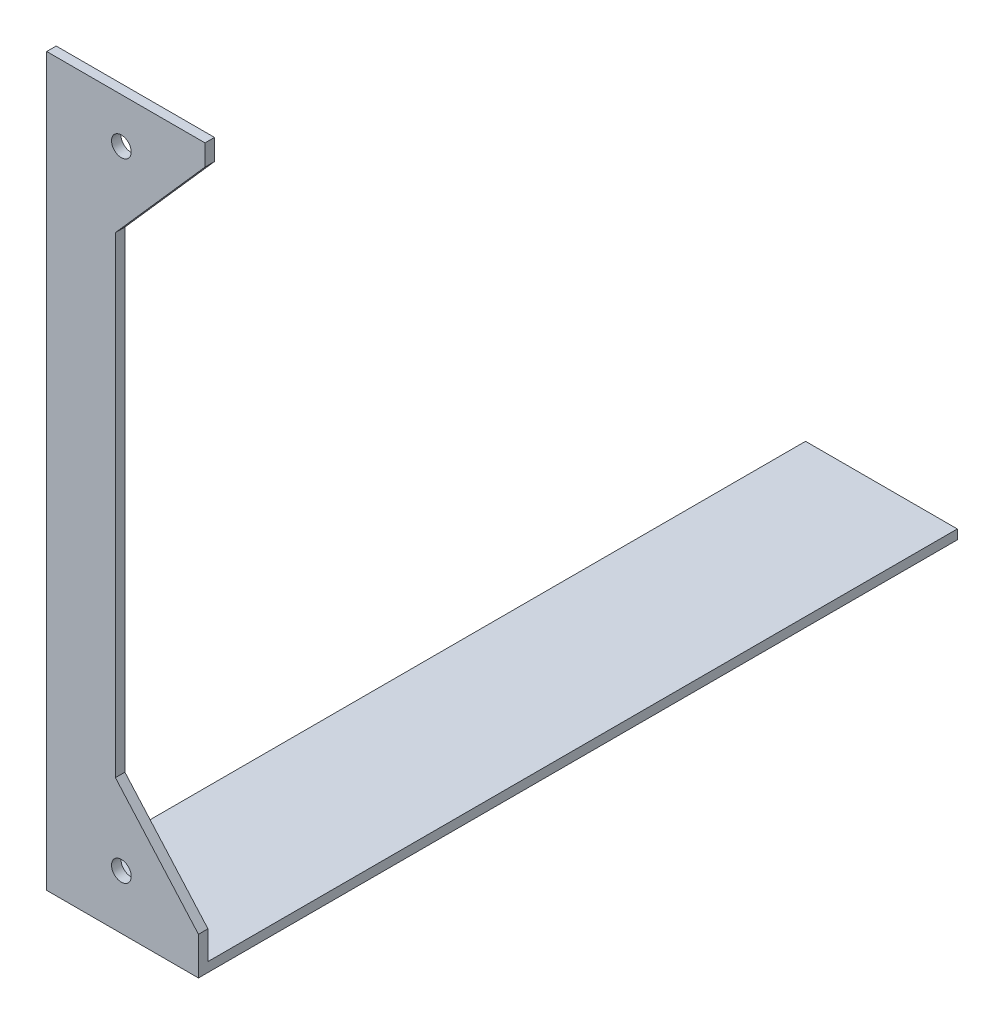
SolidWorks part; units mm, degrees
ref_plane "Front Plane" through (0, 0, 0) normal (0, 0, 1) x (1, 0, 0)
ref_plane "Top Plane" through (0, 0, 0) normal (0, 1, 0) x (1, 0, 0)
ref_plane "Right Plane" through (0, 0, 0) normal (1, 0, 0) x (0, 0, -1)
sketch "Sketch1" plane through (0, 0, 0) normal (0, 0, 1) x (1, 0, 0)
  line L0 (-250, 120) -> (0, 120) construction
  line L1 (-238.5, 99.5) -> (-223.5, 116.5) construction
  line L2 (-244.6, 99.5) -> (-238.5, 99.5) construction
  line L3 (-244.6, 20.5) -> (-244.6, 99.5) construction
  line L4 (-250, 2) -> (-250, 118) construction
  line L5 (0, 0) -> (-250, 0) construction
  line L6 (-238.5, 20.5) -> (-244.6, 20.5) construction
  line L7 (-223.5, 3.5) -> (-238.5, 20.5) construction
  line L8 (-250, 120) -> (-223.5, 120)
  line L9 (-238.5, 99.5) -> (-223.5, 116.5)
  line L10 (-244.6, 99.5) -> (-238.5, 99.5)
  line L11 (-244.6, 20.5) -> (-244.6, 99.5)
  line L12 (-250, 0) -> (-250, 120)
  line L13 (-223.5, 0) -> (-250, 0)
  line L14 (-238.5, 20.5) -> (-244.6, 20.5)
  line L15 (-223.5, 3.5) -> (-238.5, 20.5)
  line L16 (-223.5, 116.5) -> (-223.5, 120)
  line L17 (-223.5, 3.5) -> (-223.5, 0)
  line L18 (-238.5, 20.5) -> (-238.5, 99.5)
  line L19 (-224.6, 4.7467) -> (-224.6, 0)
  arc A0 (-239.15, 112.5) -> (-235.85, 112.5) centre (-237.5, 112.5) ccw construction
  arc A1 (-235.85, 112.5) -> (-239.15, 112.5) centre (-237.5, 112.5) ccw construction
  arc A2 (-235.85, 7.5) -> (-239.15, 7.5) centre (-237.5, 7.5) ccw construction
  arc A3 (-239.15, 7.5) -> (-235.85, 7.5) centre (-237.5, 7.5) ccw construction
  arc A4 (-239.15, 112.5) -> (-235.85, 112.5) centre (-237.5, 112.5) ccw
  arc A5 (-235.85, 112.5) -> (-239.15, 112.5) centre (-237.5, 112.5) ccw
  arc A6 (-235.85, 7.5) -> (-239.15, 7.5) centre (-237.5, 7.5) ccw
  arc A7 (-239.15, 7.5) -> (-235.85, 7.5) centre (-237.5, 7.5) ccw
  dimension "D1" = 25.4
extrude "Boss-Extrude1" add sketch "Sketch1" along normal blind 1.5875 contours L14 L18 L10 L11 | L17 L15 L14 L11 L10 L9 L16 L8 L12 L13 A7 A6 A5 A4 region at (-236.75, 118.7711, 0) region at (-241.55, 60, 0)
sketch "Sketch2" plane through (0, 0, 0) normal (0, 1, 0) x (1, 0, 0)
  line L1 (-250, -1.5875) -> (-250, 125.4125)
  line L2 (-250, 125.4125) -> (-224.6, 125.4125)
  line L3 (-224.6, 125.4125) -> (-224.6, -1.5875)
  line L4 (-224.6, -1.5875) -> (-250, -1.5875) construction
  line L5 (-224.6, -1.5875) -> (-250, -1.5875)
  point P5 (-223.5, -1.5875)
  point P7 (0, 0)
  point P8 (-217.7772, -2.0783)
  point P10 (-224.6, -2.2766)
  dimension "D1" = 127
extrude "Boss-Extrude2" add sketch "Sketch2" against normal blind 1.5875 contours L3 L5 L1 L2
